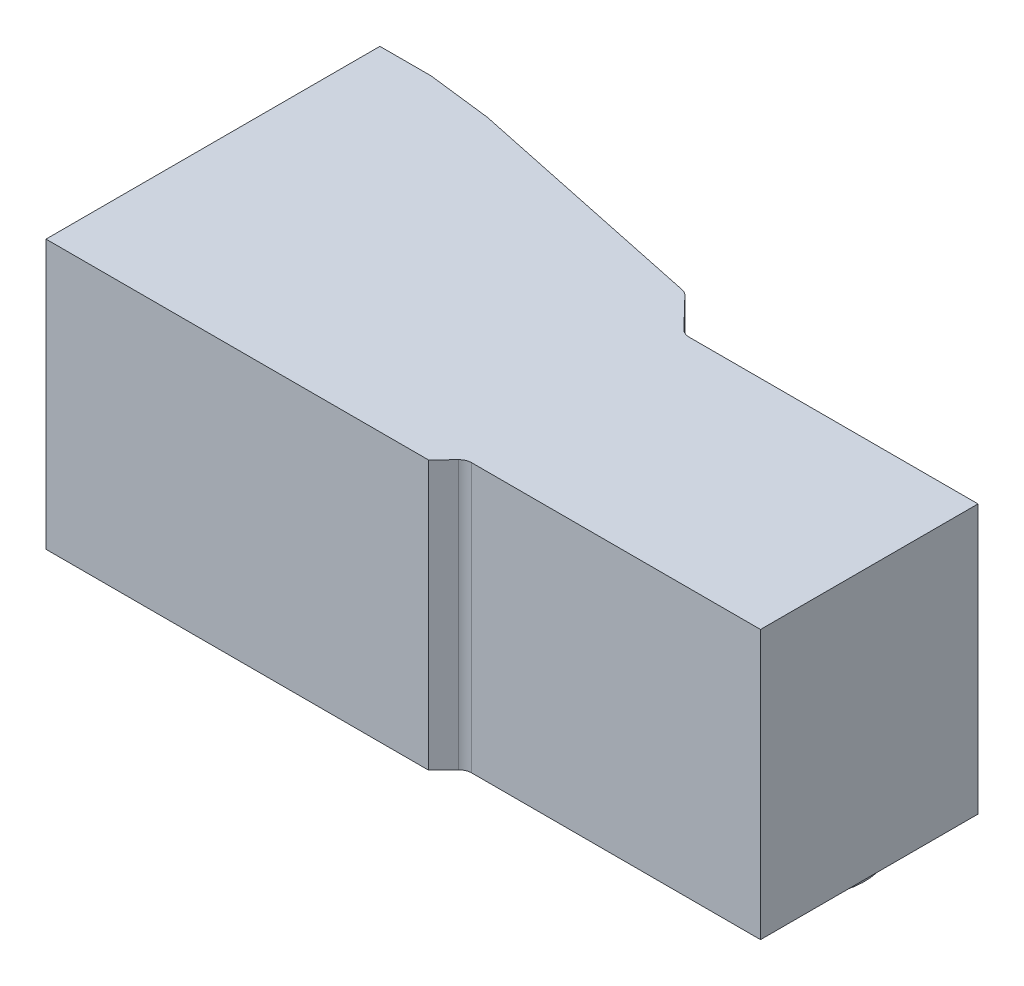
SolidWorks part; units mm, degrees
ref_plane "Front Plane" through (0, 0, 0) normal (0, 0, 1) x (1, 0, 0)
ref_plane "Top Plane" through (0, 0, 0) normal (0, 1, 0) x (1, 0, 0)
ref_plane "Right Plane" through (0, 0, 0) normal (1, 0, 0) x (0, 0, -1)
sketch "Sketch1" plane through (0, 0, 0) normal (0, 1, 0) x (1, 0, 0)
  line L0 (0, 0) -> (-459.2453, 0) construction
  line L1 (-177.1698, 160.9994) -> (-137.1698, 160.9994)
  line L2 (-137.1698, 160.9994) -> (-87.1698, 154.9616)
  line L3 (-87.1698, 154.9616) -> (108.5401, 113.7595)
  line L4 (108.5401, 113.7595) -> (136.341, 85)
  line L5 (136.341, 85) -> (366.341, 85)
  line L6 (136.341, -85) -> (366.341, -85)
  line L7 (108.5401, -113.7595) -> (136.341, -85)
  line L8 (-87.1698, -154.9616) -> (108.5401, -113.7595)
  line L9 (-137.1698, -160.9994) -> (-87.1698, -154.9616)
  line L10 (-177.1698, -160.9994) -> (-137.1698, -160.9994)
  line L11 (366.341, -85) -> (366.341, 85)
  line L12 (-177.1698, -160.9994) -> (-177.1698, 160.9994)
  dimension "D1" = 40
  dimension "D2" = 50
  dimension "D3" = 200
  dimension "D4" = 40
  dimension "D5" = 230
  dimension "D6" = 170
extrude "Boss-Extrude1" add sketch "Sketch1" along normal blind 210
ref_plane "Plane1" through (0, 0, 160) normal (0, 0, 1) x (1, 0, 0)
sketch "Sketch2" plane through (0, 0, 160) normal (0, 0, 1) x (1, 0, 0)
  line L0 (-177.1698, 0) -> (366.341, 145)
  line L1 (366.341, 145) -> (366.341, 0)
  line L2 (366.341, 0) -> (-177.1698, 0)
  line L3 (366.341, 210) -> (366.341, 0) construction
  dimension "D1" = 145
extrude "Cut-Extrude1" cut sketch "Sketch2" against normal blind 60
fillet "Fillet1" radius 10 4 edges at (136.341, 105, 85) (108.5401, 143.1114, 113.7595) (-87.1698, 117.0053, 154.9616) (-137.1698, 105, 160.9994)
fillet "Fillet2" radius 10 4 edges at (-137.1698, 105, -160.9994) (-87.1698, 105, -154.9616) (108.5401, 105, -113.7595) (136.341, 105, -85)
sketch "Sketch3" plane through (0, 0, 0) normal (0, -1, 0) x (1, 0, 0)
  circle A0 centre (312.6057, 0) radius 50
extrude "Boss-Extrude2" add sketch "Sketch3" along normal blind 5
sketch "Sketch4" plane through (0, 0, 0) normal (0, -1, 0) x (1, 0, 0)
  line L1 (-177.1698, 100) -> (126.1422, 100)
  line L2 (-177.1698, 100) -> (-177.1698, 203.5752)
  line L3 (-177.1698, 203.5752) -> (126.1422, 203.5752)
  line L4 (126.1422, 100) -> (126.1422, 203.5752)
extrude "Cut-Extrude2" cut sketch "Sketch4" along normal through all both and the other way through all
